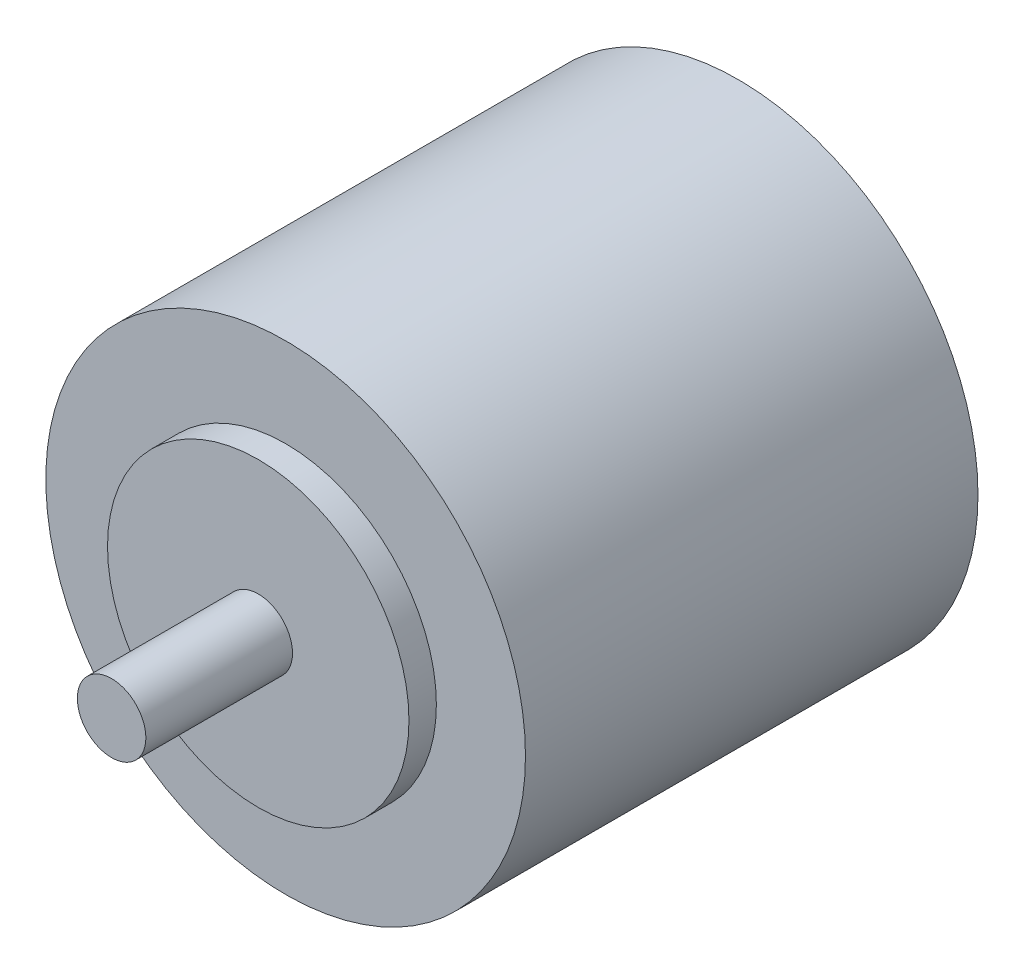
SolidWorks part; units mm, degrees
ref_plane "Front Plane" through (0, 0, 0) normal (0, 0, 1) x (1, 0, 0)
ref_plane "Top Plane" through (0, 0, 0) normal (0, 1, 0) x (1, 0, 0)
ref_plane "Right Plane" through (0, 0, 0) normal (1, 0, 0) x (0, 0, -1)
ref_plane "Plane1" through (0, 0, 33.02) normal (0, 0, 1) x (1, 0, 0)
sketch "Sketch1" plane through (0, 0, 33.02) normal (0, 0, 1) x (1, 0, 0)
  circle A0 centre (0, 0) radius 17.5
  dimension "D1" = 35
extrude "Boss-Extrude1" add sketch "Sketch1" against normal blind 33.02
ref_plane "Plane2" through (0, 0, 2.2098) normal (0, 0, -1) x (-1, 0, 0)
sketch "Sketch6" plane through (0, 0, 0) normal (0, 1, 0) x (1, 0, 0)
  line L0 (10.9982, -33.02) -> (0, -33.02)
  line L1 (0, -33.02) -> (0, -45.72)
  line L2 (0, -45.72) -> (2.5, -45.72)
  line L3 (2.5, -45.72) -> (2.5, -35.02)
  line L4 (2.5, -35.02) -> (10.9982, -35.02)
  line L5 (10.9982, -35.02) -> (10.9982, -33.02)
  line L6 (0, -33.02) -> (0, -45.72) construction
  line L7 (-55, -33.02) -> (55, -33.02) construction
  line L9 (-17.5, -33.02) -> (17.5, -33.02) construction
  dimension "D1" = 12.7
  dimension "D2" = 2
  dimension "D3" = 10.9982
  dimension "D6" = 2.5
revolve "Revolve5" add sketch "Sketch6" angle 360 about L6 reverse direction yes
